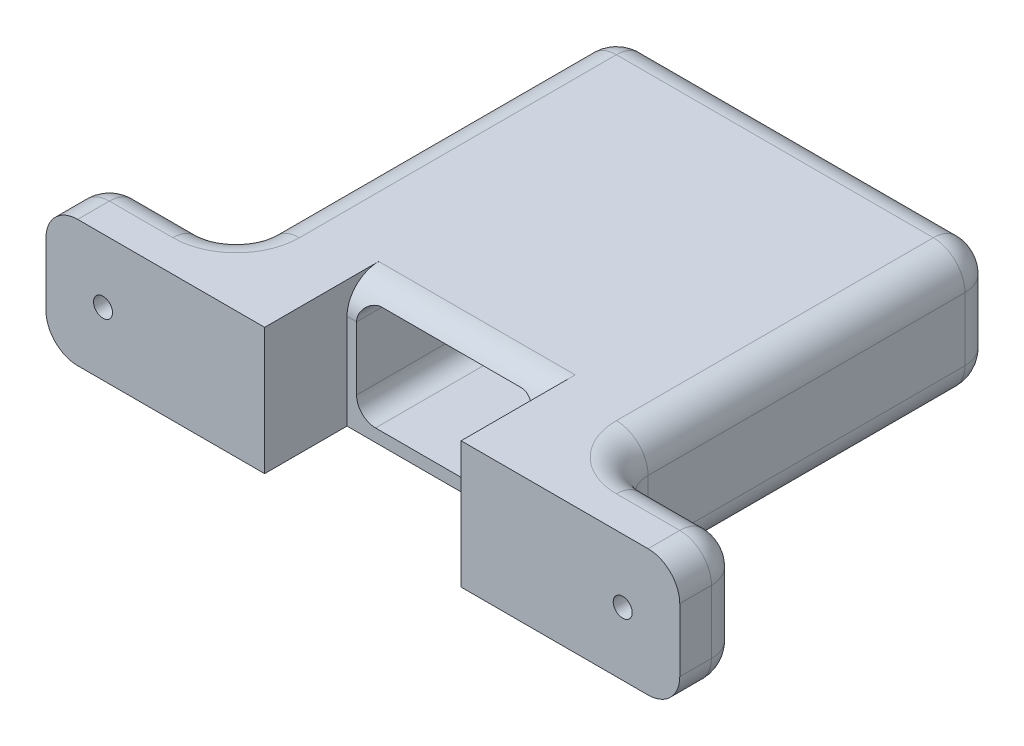
SolidWorks part; units mm, degrees
material "ABS"
ref_plane "Plano frontal" through (0, 0, 0) normal (0, 0, 1) x (1, 0, 0)
ref_plane "Plano superior" through (0, 0, 0) normal (0, 1, 0) x (1, 0, 0)
ref_plane "Plano direito" through (0, 0, 0) normal (1, 0, 0) x (0, 0, -1)
sketch "Esboço1" plane through (0, 0, 0) normal (0, 0, 1) x (1, 0, 0)
  line L1 (-92.8694, -28.0887) -> (-32.8694, -28.0887)
  line L2 (-92.8694, -28.0887) -> (-92.8694, -8.0887)
  line L3 (-92.8694, -8.0887) -> (-32.8694, -8.0887)
  line L4 (-32.8694, -28.0887) -> (-32.8694, -8.0887)
  dimension "D1" = 20
  dimension "D2" = 60
extrude "Ressalto-extrusão1" add sketch "Esboço1" along normal blind 70
sketch "Esboço4" plane through (0, -28.0887, 0) normal (0, -1, 0) x (-1, 0, 0)
  line L0 (32.8694, -70) -> (32.8694, 0) construction
  line L1 (47.3694, -70) -> (78.3694, -70)
  line L2 (47.3694, -70) -> (47.3694, -57)
  line L3 (47.3694, -57) -> (78.3694, -57)
  line L4 (78.3694, -70) -> (78.3694, -57)
  line L7 (32.8694, -70) -> (92.8694, -70) construction
  point P4 (47.3694, -63.5)
  dimension "D1" = 31
  dimension "D2" = 13
  dimension "D3" = 14.5
  dimension "D4" = 0
extrude "Corte-extrusão2" cut sketch "Esboço4" against normal through all
sketch "Esboço5" plane through (-32.8694, 0, 0) normal (1, 0, 0) x (0, 0, -1)
  line L0 (-70, -8.0887) -> (0, -8.0887) construction
  line L1 (-70, -28.0887) -> (-60, -28.0887)
  line L2 (-70, -28.0887) -> (-70, -8.0887)
  line L3 (-70, -8.0887) -> (-60, -8.0887)
  line L4 (-60, -28.0887) -> (-60, -8.0887)
  dimension "D1" = 10
sketch "Esboço6" plane through (-92.8694, 0, 0) normal (-1, 0, 0) x (0, 0, 1)
  line L0 (70, -8.0887) -> (0, -8.0887) construction
  line L1 (70, -28.0887) -> (60, -28.0887)
  line L2 (70, -28.0887) -> (70, -8.0887)
  line L3 (70, -8.0887) -> (60, -8.0887)
  line L4 (60, -28.0887) -> (60, -8.0887)
  dimension "D1" = 10
extrude "Ressalto-extrusão2" add sketch "Esboço6" along normal blind 20
extrude "Ressalto-extrusão3" add sketch "Esboço5" along normal blind 20
sketch "Esboço7" plane through (0, 0, 0) normal (0, 0, -1) x (-1, 0, 0)
  line L0 (92.8694, -28.0887) -> (32.8694, -28.0887) construction
  line L1 (73.8694, -26.0887) -> (51.8694, -26.0887)
  line L2 (76.8694, -23.0887) -> (76.8694, -13.0887)
  line L3 (73.8694, -10.0887) -> (51.8694, -10.0887)
  line L4 (48.8694, -23.0887) -> (48.8694, -13.0887)
  line L5 (32.8694, -8.0887) -> (92.8694, -8.0887) construction
  line L6 (32.8694, -28.0887) -> (32.8694, -8.0887) construction
  line L7 (92.8694, -8.0887) -> (92.8694, -28.0887) construction
  arc A0 (76.8694, -13.0887) -> (73.8694, -10.0887) centre (73.8694, -13.0887) ccw
  arc A1 (51.8694, -10.0887) -> (48.8694, -13.0887) centre (51.8694, -13.0887) ccw
  arc A2 (51.8694, -26.0887) -> (48.8694, -23.0887) centre (51.8694, -23.0887) cw
  arc A3 (73.8694, -26.0887) -> (76.8694, -23.0887) centre (73.8694, -23.0887) ccw
  dimension "D5" = 3
  dimension "D1" = 2
  dimension "D2" = 2
  dimension "D3" = 16
  dimension "D4" = 16
extrude "Corte-extrusão4" cut sketch "Esboço7" against normal up to next
fillet "Filete1" radius 5 20 edges at (-102.8694, -8.0887, 60) (-22.8694, -28.0887, 60) (-22.8694, -8.0887, 60) (-12.8694, -8.0887, 65) (-112.8694, -8.0887, 65) (-112.8694, -28.0887, 65) (-12.8694, -28.0887, 65) (-112.8694, -18.0887, 60) (-102.8694, -28.0887, 60) (-92.8694, -18.0887, 60) (-12.8694, -18.0887, 60) (-32.8694, -18.0887, 60) (-32.8694, -28.0887, 30) (-32.8694, -8.0887, 30) (-92.8694, -8.0887, 30) (-92.8694, -28.0887, 30) (-62.8694, -28.0887, 0) (-92.8694, -18.0887, 0) (-62.8694, -8.0887, 0) (-32.8694, -18.0887, 0)
sketch "Esboço8" plane through (0, 0, 60) normal (0, 0, -1) x (-1, 0, 0)
  line L0 (17.8694, -23.0887) -> (27.8694, -23.0887) construction
  line L4 (97.8694, -13.0887) -> (97.8694, -23.0887) construction
  line L5 (97.8694, -23.0887) -> (107.8694, -23.0887) construction
  line L6 (27.8694, -23.0887) -> (27.8694, -13.0887) construction
  circle A0 centre (21.8694, -18.0887) radius 1.5
  circle A1 centre (103.8694, -18.0887) radius 1.5
  point P10 (27.8694, -18.0887)
  point P11 (97.8694, -18.0887)
  dimension "D1" = 3
  dimension "D2" = 3
  dimension "D3" = 5
  dimension "D4" = 6
  dimension "D5" = 6
  dimension "D6" = 5
extrude "Corte-extrusão5" cut sketch "Esboço8" against normal through all
fillet "Filete2" radius 5 1 edges at (-62.8694, -8.0887, 57)
